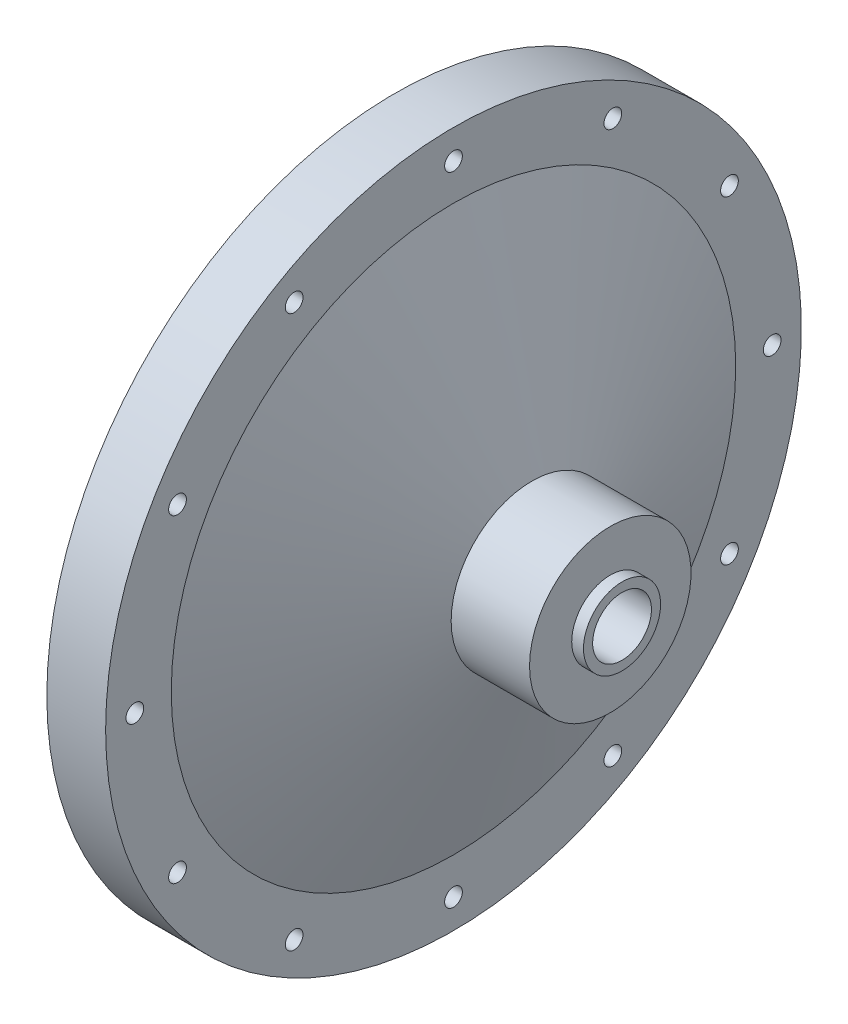
SolidWorks part; units mm, degrees
material "6061-T6 (SS)"
ref_plane "Front Plane" through (0, 0, 0) normal (0, 0, 1) x (1, 0, 0)
ref_plane "Top Plane" through (0, 0, 0) normal (0, 1, 0) x (1, 0, 0)
ref_plane "Right Plane" through (0, 0, 0) normal (1, 0, 0) x (0, 0, -1)
sketch "Sketch2" plane through (0, 0, 0) normal (0, 0, 1) x (1, 0, 0)
  line L0 (0, 0) -> (165.0115, 0) construction
  line L1 (0, 0) -> (0, 56.3562)
  line L2 (0, 56.3562) -> (9.525, 56.3562)
  line L3 (9.525, 56.3562) -> (9.525, 45.72)
  line L4 (9.525, 45.72) -> (22.225, 13.081)
  line L5 (34.925, 13.081) -> (34.925, 6.2484)
  line L6 (22.225, 13.081) -> (34.925, 13.081)
  line L7 (34.925, 6.2484) -> (36.83, 6.2484)
  line L8 (36.83, 6.2484) -> (36.83, 0)
  line L9 (0, 0) -> (36.83, 0)
  dimension "D1" = 56.3562
  dimension "D2" = 9.525
  dimension "D3" = 45.72
  dimension "D4" = 13.081
  dimension "D5" = 12.7
  dimension "D6" = 12.7
  dimension "D7" = 6.2484
  dimension "D8" = 1.905
revolve "Main Structure" add sketch "Sketch2" angle 360 about L0
cosmetic thread "Cosmetic Thread1" parameters "D2"=23.1953
sketch "Sketch3" plane through (36.83, 0, 0) normal (1, 0, 0) x (0, 0, -1)
  circle A0 centre (0, 0) radius 4.7625
  dimension "D1" = 9.525
extrude "Oxidizer Inlet Hole" cut sketch "Sketch3" against normal through all
sketch "Sketch4" plane through (0, 0, 0) normal (-1, 0, 0) x (0, 0, 1)
  circle A0 centre (0, 0) radius 51.6255 construction
  circle A1 centre (0, -51.6255) radius 2.146
  circle A2 centre (-25.8127, -44.709) radius 2.146
  circle A3 centre (-44.709, -25.8128) radius 2.146
  circle A4 centre (-51.6255, 0) radius 2.146
  circle A5 centre (-44.709, 25.8127) radius 2.146
  circle A6 centre (-25.8128, 44.709) radius 2.146
  circle A7 centre (0, 51.6255) radius 2.146
  circle A8 centre (25.8127, 44.709) radius 2.146
  circle A9 centre (44.709, 25.8128) radius 2.146
  circle A10 centre (51.6255, 0) radius 2.146
  circle A11 centre (44.709, -25.8127) radius 2.146
  circle A12 centre (25.8128, -44.709) radius 2.146
  point P29 (0, 0)
  dimension "D1" = 12
  dimension "D2" = 103.251
hole_wizard "Flange Holes" positions "Sketch7" profile "Sketch8" hole size "#33" standard "ANSI Inch"
sketch "Sketch7" plane through (0, 0, 0) normal (-1, 0, 0) x (0, 0, 1)
  point P0 (0, -51.6255)
  point P3 (-25.8127, -44.709)
  point P6 (-44.709, -25.8128)
  point P9 (-51.6255, 0)
  point P12 (-44.709, 25.8127)
  point P15 (-25.8128, 44.709)
  point P18 (0, 51.6255)
  point P21 (25.8127, 44.709)
  point P24 (44.709, 25.8128)
  point P27 (51.6255, 0)
  point P30 (44.709, -25.8127)
  point P33 (25.8128, -44.709)
sketch "Sketch8" plane through (0, -51.6255, 0) normal (0, 1, 0) x (0, 0, 1)
  line L0 (0, 0) -> (0, 26.2623)
  line L1 (0, 26.2623) -> (1.4351, 25.4)
  line L2 (1.4351, 25.4) -> (1.4351, 0)
  line L5 (1.4351, 0) -> (0, 0)
  line L10 (0, 26.2623) -> (-1.4351, 25.4) construction
  line L11 (0, -6.35) -> (0, 107.95) construction
  dimension "Hole Dia." = 2.8702
  dimension "Hole Depth" = 25.4
  dimension "Drill Angle" = 118
sketch "Sketch9" plane through (0, 0, 0) normal (-1, 0, 0) x (0, 0, 1)
  line L0 (0, 0) -> (-67.6727, 18.1329) construction
  line L1 (0, 0) -> (-51.6255, 0) construction
  circle A0 centre (0, 0) radius 51.6255 construction
  circle A1 centre (-49.8664, 13.3617) radius 2.9451
  circle A2 centre (48.7255, -13.056) radius 2.9451
  point P14 (-0.5704, 0.1528)
  dimension "D1" = 15
  dimension "D2" = 2
hole_wizard "Dowel Holes" positions "Sketch10" profile "Sketch11" hole size "3/16" standard "ANSI Inch"
sketch "Sketch10" plane through (0, 0, 0) normal (-1, 0, 0) x (0, 0, 1)
  point P0 (48.7255, -13.056)
  point P3 (-49.8664, 13.3617)
sketch "Sketch11" plane through (0, -13.056, 48.7255) normal (0, 1, 0) x (0, 0, 1)
  line L0 (0, 0) -> (0, 7.7808)
  line L1 (0, 7.7808) -> (2.3812, 6.35)
  line L2 (2.3812, 6.35) -> (2.3812, 0)
  line L5 (2.3812, 0) -> (0, 0)
  line L10 (0, 7.7808) -> (-2.3812, 6.35) construction
  line L11 (0, -6.35) -> (0, 107.95) construction
  dimension "Hole Dia." = 4.7625
  dimension "Hole Depth" = 6.35
  dimension "Drill Angle" = 118
sketch "Sketch12" plane through (0, 0, 0) normal (-1, 0, 0) x (0, 0, 1)
  circle A0 centre (0, 0) radius 38.1
  dimension "D1" = 76.2
extrude "Impinging Plate Flat Cut" cut sketch "Sketch12" against normal blind 3.81
ref_plane "Plane1" through (6.35, 0, 0) normal (-1, 0, 0) x (0, 0, 1)
sketch "Sketch14" plane through (3.81, 0, 0) normal (-1, 0, 0) x (0, 0, 1)
  circle A0 centre (0, 0) radius 38.1
  dimension "D1" = 76.2
sketch "Sketch15" plane through (6.35, 0, 0) normal (-1, 0, 0) x (0, 0, 1)
  circle A0 centre (0, 0) radius 38.0873
  dimension "D1" = 76.1746
loft "Impinging Plate Taper Cut" cut profiles "Sketch14", "Sketch15" connector at (3.81, 0, 38.1) connector at (6.35, 0, 38.0873)
sketch "Sketch16" plane through (6.35, 0, 0) normal (-1, 0, 0) x (0, 0, 1)
  circle A0 centre (0, 0) radius 28.575
  dimension "D1" = 57.15
ref_plane "Plane2" through (21.59, 0, 0) normal (-1, 0, 0) x (0, 0, 1)
sketch "Sketch17" plane through (21.59, 0, 0) normal (-1, 0, 0) x (0, 0, 1)
  circle A0 centre (0, 0) radius 4.7625
  dimension "D1" = 9.525
loft "Internal Flow Path Loft Cut" cut profiles "Sketch16", "Sketch17" connector at (6.35, 0, 28.575) connector at (21.59, 0, 4.7625)
fillet "Internal Fillet" radius 3.175 1 edges at (21.59, 0, 4.7625)
sketch "Sketch18" plane through (6.35, 0, 0) normal (-1, 0, 0) x (0, 0, 1)
  circle A0 centre (0, 0) radius 33.3375
  circle A1 centre (33.3375, 0) radius 1.5042
  dimension "D1" = 66.675
hole_wizard "4-40 Tapped Holes " positions "Sketch19" profile "Sketch20" hole size "#4-40" standard "ANSI Inch"
sketch "Sketch19" plane through (6.35, 0, 0) normal (-1, 0, 0) x (0, 0, 1)
  point P0 (33.3375, 0)
sketch "Sketch20" plane through (6.35, 0, 33.3375) normal (0, 1, 0) x (0, 0, 1)
  line L0 (0, 0) -> (0, 5.4417)
  line L1 (0, 5.4417) -> (1.1303, 4.7625)
  line L2 (1.1303, 4.7625) -> (1.1303, 0)
  line L5 (1.1303, 0) -> (0, 0)
  line L10 (0, 5.4417) -> (-1.1303, 4.7625) construction
  line L11 (0, -6.35) -> (0, 107.95) construction
  dimension "Hole Dia." = 2.2606
  dimension "Hole Depth" = 4.7625
  dimension "Drill Angle" = 118
pattern_circular "Extended 8 BC" count 8 over 360 about axis through (3.81, 0, 0) along (-1, 0, 0) of "4-40 Tapped Holes "
chamfer "Chamfer for Impinging Edge" distance 0.127 angle 45 1 edges at (6.35, 0, 38.0873) first distance on face at (3.81, 0, 38.1)
